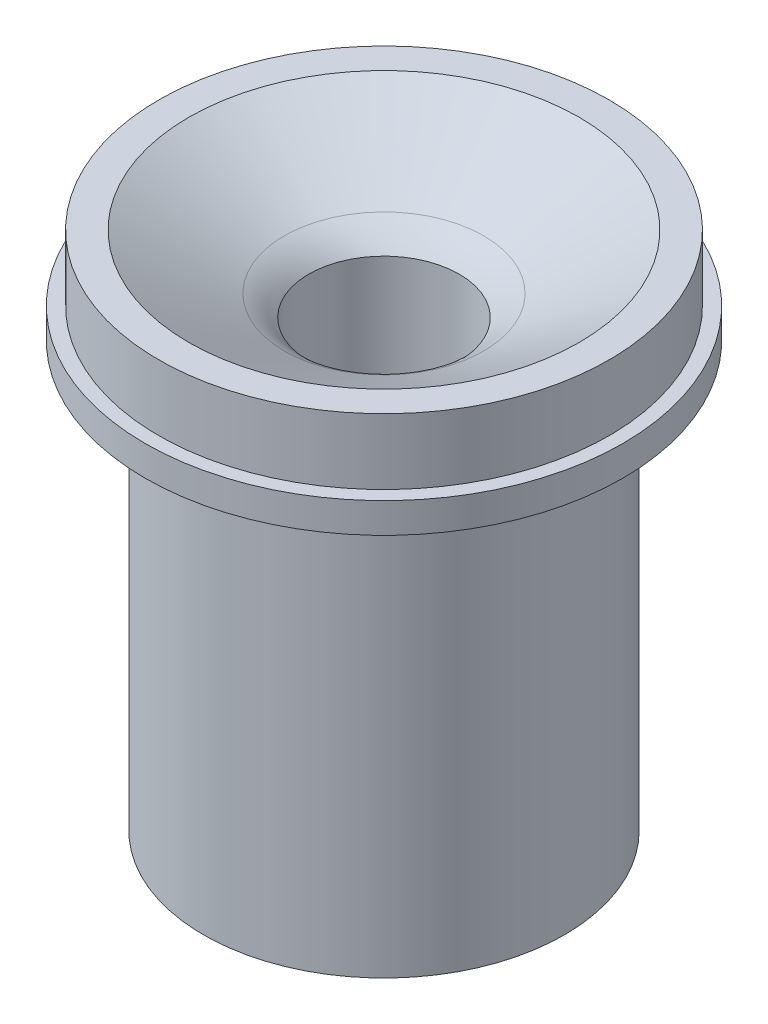
SolidWorks part; units mm, degrees
ref_plane "Front Plane" through (0, 0, 0) normal (0, 0, 1) x (1, 0, 0)
ref_plane "Top Plane" through (0, 0, 0) normal (0, 1, 0) x (1, 0, 0)
ref_plane "Right Plane" through (0, 0, 0) normal (1, 0, 0) x (0, 0, -1)
sketch "Sketch1" plane through (0, 0, 0) normal (0, 0, 1) x (1, 0, 0)
  line L0 (0, 0) -> (0, 60.0489) construction
  line L1 (15.875, -54.9402) -> (5.7719, -17.2349)
  line L2 (5.7719, -17.2349) -> (5.7719, -14.0599)
  line L3 (10.5344, -5.811) -> (20.5994, 0)
  line L4 (20.5994, 0) -> (23.7744, 0)
  line L5 (23.7744, 0) -> (23.7744, -6.9342)
  line L6 (23.7744, -6.9342) -> (25.2095, -6.9342)
  line L7 (25.2095, -6.9342) -> (25.2095, -10.1092)
  line L8 (25.2095, -10.1092) -> (22.2123, -10.1092)
  line L9 (22.2123, -10.1092) -> (22.2123, -11.8872)
  line L10 (22.2123, -11.8872) -> (19.05, -11.8872)
  line L11 (19.05, -11.8872) -> (19.05, -54.9402)
  line L12 (15.875, -54.9402) -> (19.05, -54.9402)
  line L13 (-15.875, -54.9402) -> (-19.05, -54.9402)
  line L14 (-19.05, -11.8872) -> (-19.05, -54.9402)
  line L15 (-22.2123, -11.8872) -> (-19.05, -11.8872)
  line L16 (-22.2123, -10.1092) -> (-22.2123, -11.8872)
  line L17 (-25.2095, -10.1092) -> (-22.2123, -10.1092)
  line L18 (-25.2095, -6.9342) -> (-25.2095, -10.1092)
  line L19 (-23.7744, -6.9342) -> (-25.2095, -6.9342)
  line L20 (-23.7744, 0) -> (-23.7744, -6.9342)
  line L21 (-20.5994, 0) -> (-23.7744, 0)
  line L22 (-10.5344, -5.811) -> (-20.5994, 0)
  line L23 (-5.7719, -17.2349) -> (-5.7719, -14.0599)
  line L24 (-15.875, -54.9402) -> (-5.7719, -17.2349)
  line L25 (-20.447, -11.8872) -> (-19.05, -13.2842)
  line L26 (20.447, -11.8872) -> (19.05, -13.2842)
  arc A0 (5.7719, -14.0599) -> (10.5344, -5.811) centre (15.2969, -14.0599) cw
  arc A1 (-10.5344, -5.811) -> (-5.7719, -14.0599) centre (-15.2969, -14.0599) cw
  point P17 (10.5344, -27.9579)
  point P34 (5.7719, -8.5607)
  point P37 (-5.7719, -8.5607)
  point P38 (-20.447, -1.4116)
  point P39 (-5.7719, -8.5607)
  dimension "D15" = 9.525
  dimension "D1" = 50.419
  dimension "D2" = 47.5488
  dimension "D3" = 41.1988
  dimension "D4" = 6.9342
  dimension "D5" = 10.1092
  dimension "D6" = 11.8872
  dimension "D7" = 13.2842
  dimension "D8" = 40.894
  dimension "D9" = 120
  dimension "D10" = 30
  dimension "D11" = 31.75
  dimension "D12" = 38.1
  dimension "D13" = 44.4246
  dimension "D14" = 54.9402
  dimension "D16" = 3.175
revolve "Revolve1" add sketch "Sketch1" angle 360 about L0 region at (14.8502, -22.8617, 0) region at (19.5157, -12.3529, 0)
sketch "Sketch2" plane through (0, 0, 0) normal (0, 1, 0) x (1, 0, 0)
  circle A0 centre (0, 0) radius 7.9375
  dimension "D1" = 15.875
extrude "Cut-Extrude1" cut sketch "Sketch2" against normal through all both and the other way through all
